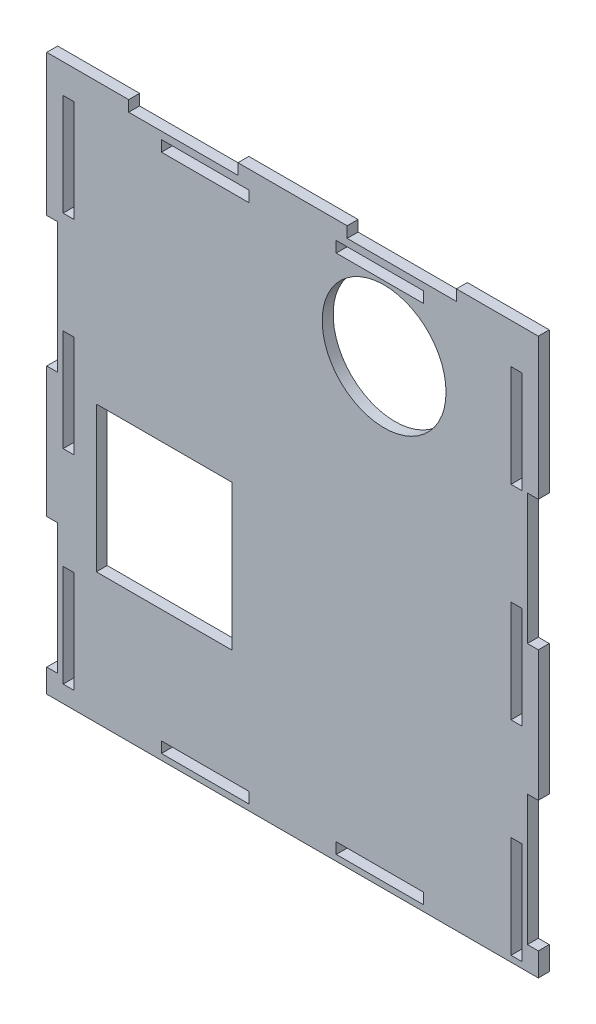
SolidWorks part; units mm, degrees
ref_plane "Front Plane" through (0, 0, 0) normal (0, 0, 1) x (1, 0, 0)
ref_plane "Top Plane" through (0, 0, 0) normal (0, 1, 0) x (1, 0, 0)
ref_plane "Right Plane" through (0, 0, 0) normal (1, 0, 0) x (0, 0, -1)
sketch "Sketch1" plane through (0, 0, 0) normal (0, 0, 1) x (1, 0, 0)
  line L1 (0, 0) -> (129, 0)
  line L2 (0, 6.45) -> (0, 42.25)
  line L3 (19.5, 149.65) -> (49.5, 149.65)
  line L4 (129, 6.45) -> (129, 42.25)
  line L5 (0, 152.65) -> (19.5, 152.65)
  line L6 (19.5, 152.65) -> (19.5, 149.65)
  line L7 (49.5, 149.65) -> (49.5, 152.65)
  line L8 (49.5, 152.65) -> (79.5, 152.65)
  line L9 (79.5, 152.65) -> (79.5, 149.65)
  line L11 (129, 152.65) -> (109.5, 152.65)
  line L12 (109.5, 152.65) -> (109.5, 149.65)
  line L13 (79.5, 149.65) -> (109.5, 149.65)
  line L15 (132, 149.65) -> (132, 113.85)
  line L16 (132, 113.85) -> (129, 113.85)
  line L17 (129, 78.05) -> (132, 78.05)
  line L18 (132, 78.05) -> (132, 42.25)
  line L19 (132, 42.25) -> (129, 42.25)
  line L20 (129, 6.45) -> (132, 6.45)
  line L21 (132, 6.45) -> (132, 0)
  line L22 (129, 78.05) -> (129, 113.85)
  line L23 (129, 0) -> (132, 0)
  line L24 (132, 149.65) -> (132, 152.65)
  line L25 (132, -29.35) -> (129, -29.35) [skipped]
  line L26 (132, 152.65) -> (129, 152.65)
  line L28 (-3, 149.65) -> (-3, 113.85)
  line L29 (-3, 113.85) -> (0, 113.85)
  line L30 (0, 78.05) -> (-3, 78.05)
  line L31 (-3, 78.05) -> (-3, 42.25)
  line L32 (-3, 42.25) -> (0, 42.25)
  line L33 (0, 6.45) -> (-3, 6.45)
  line L34 (-3, 6.45) -> (-3, 0)
  line L35 (0, 152.65) -> (-3, 152.65)
  line L36 (0, 78.05) -> (0, 113.85)
  line L37 (0, 0) -> (-3, 0)
  line L38 (-3, 152.65) -> (-3, 149.65)
  line L40 (10.6135, 75.8169) -> (47.8295, 75.8169)
  line L41 (10.6135, 75.8169) -> (10.6135, 35.9035)
  line L42 (10.6135, 35.9035) -> (47.8295, 35.9035)
  line L43 (47.8295, 75.8169) -> (47.8295, 35.9035)
  line L65 (76.5, 147.65) -> (100.5, 147.65)
  line L66 (76.5, 147.65) -> (76.5, 144.65)
  line L88 (76.5, 144.65) -> (100.5, 144.65)
  line L89 (100.5, 147.65) -> (100.5, 144.65)
  line L90 (76.5, 4.65) -> (100.5, 4.65)
  line L91 (76.5, 4.65) -> (76.5, 1.65)
  line L92 (76.5, 1.65) -> (100.5, 1.65)
  line L93 (100.5, 4.65) -> (100.5, 1.65)
  line L94 (28.5, 4.65) -> (52.5, 4.65)
  line L95 (28.5, 4.65) -> (28.5, 1.65)
  line L96 (28.5, 1.65) -> (52.5, 1.65)
  line L97 (52.5, 4.65) -> (52.5, 1.65)
  line L98 (28.5, 147.65) -> (52.5, 147.65)
  line L99 (28.5, 147.65) -> (28.5, 144.65)
  line L100 (28.5, 144.65) -> (52.5, 144.65)
  line L101 (52.5, 147.65) -> (52.5, 144.65)
  line L102 (127.5, 141.65) -> (124.5, 141.65)
  line L103 (127.5, 141.65) -> (127.5, 113.65)
  line L104 (127.5, 113.65) -> (124.5, 113.65)
  line L105 (124.5, 141.65) -> (124.5, 113.65)
  line L106 (127.5, 85.65) -> (124.5, 85.65)
  line L107 (127.5, 85.65) -> (127.5, 57.65)
  line L108 (127.5, 57.65) -> (124.5, 57.65)
  line L109 (124.5, 85.65) -> (124.5, 57.65)
  line L110 (127.5, 29.65) -> (124.5, 29.65)
  line L111 (127.5, 29.65) -> (127.5, 1.65)
  line L112 (127.5, 1.65) -> (124.5, 1.65)
  line L113 (124.5, 29.65) -> (124.5, 1.65)
  line L114 (4.5, 144.65) -> (1.5, 144.65)
  line L115 (4.5, 144.65) -> (4.5, 116.65)
  line L116 (4.5, 116.65) -> (1.5, 116.65)
  line L117 (1.5, 144.65) -> (1.5, 116.65)
  line L118 (4.5, 88.65) -> (1.5, 88.65)
  line L119 (4.5, 88.65) -> (4.5, 60.65)
  line L120 (4.5, 60.65) -> (1.5, 60.65)
  line L121 (1.5, 88.65) -> (1.5, 60.65)
  line L122 (4.5, 32.65) -> (1.5, 32.65)
  line L123 (4.5, 32.65) -> (4.5, 4.65)
  line L124 (4.5, 4.65) -> (1.5, 4.65)
  line L125 (1.5, 32.65) -> (1.5, 4.65)
  circle A1 centre (89.65, 126.65) radius 17
  dimension "D60" = 34
  dimension "D2" = 3
  dimension "D3" = 19.5
  dimension "D4" = 3
  dimension "D5" = 30
  dimension "D6" = 3
  dimension "D7" = 30
  dimension "D8" = 3
  dimension "D9" = 19.5
  dimension "D10" = 35.8
  dimension "D11" = 35.8
  dimension "D13" = 129
  dimension "D14" = 3
  dimension "D15" = 35.8
  dimension "D16" = 35.8
  dimension "D17" = 35.8
  dimension "D18" = 28
  dimension "D19" = 28
  dimension "D20" = 28
  dimension "D21" = 3
  dimension "D22" = 3
  dimension "D23" = 3
  dimension "D26" = 28
  dimension "D24" = 0
  dimension "D27" = 28
  dimension "D28" = 28
  dimension "D29" = 3
  dimension "D25" = 0
  dimension "D30" = 3
  dimension "D31" = 3
  dimension "D32" = 3
  dimension "D33" = 0
  dimension "D34" = 0
  dimension "D35" = 28
  dimension "D36" = 28
  dimension "D37" = 28
  dimension "D38" = 28
  dimension "D39" = 24
  dimension "D40" = 24
  dimension "D41" = 3
  dimension "D42" = 3
  dimension "D43" = 0
  dimension "D44" = 24
  dimension "D45" = 24
  dimension "D46" = 3
  dimension "D47" = 3
  dimension "D48" = 0
  dimension "D49" = 0
  dimension "D50" = 0
  dimension "D51" = 0
  dimension "D52" = 24
  dimension "D53" = 149.65
  dimension "D54" = 24
  dimension "D55" = 120
  dimension "D56" = 24
  dimension "D57" = 24
  dimension "D58" = 1.65
  dimension "D59" = 1.5
  dimension "D12" = 3
extrude "Boss-Extrude1" add sketch "Sketch1" along normal blind 3 contours L5 L38 L28 L29 L36 L30 L31 L32 L2 L33 L34 L37 L1 L23 L21 L20 L4 L19 L18 L17 L22 L16 L15 L24 L26 L11 L12 L13 L9 L8 L7 L3 L6 L40 L43 L42 L41 region at (66.2587, 75.1515, 0)
